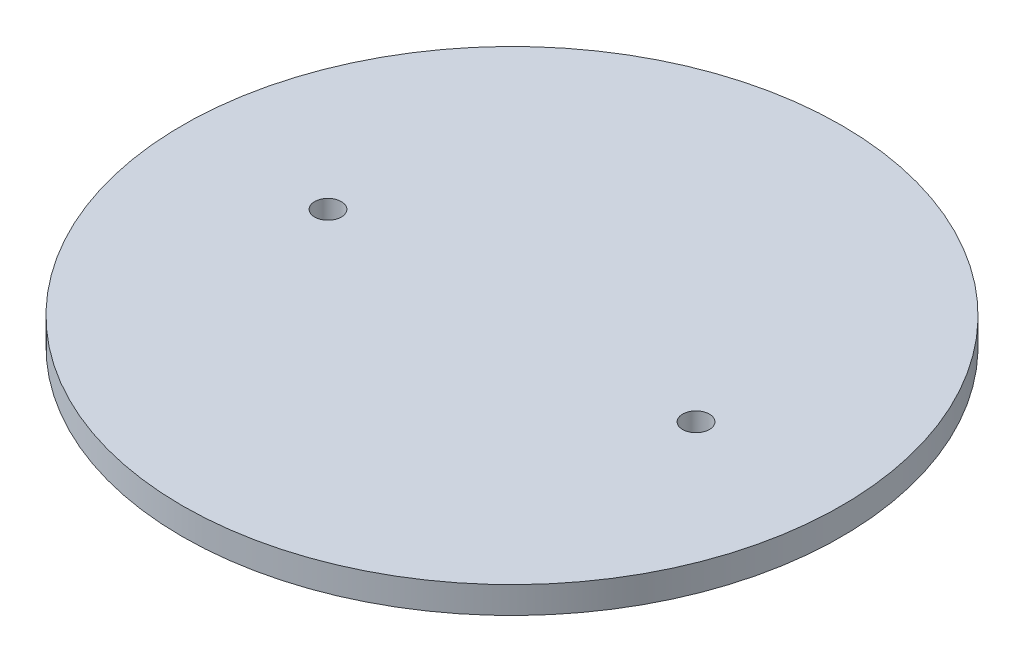
SolidWorks part; units mm, degrees
material "Balsa"
ref_plane "Front Plane" through (0, 0, 0) normal (0, 0, 1) x (1, 0, 0)
ref_plane "Top Plane" through (0, 0, 0) normal (0, 1, 0) x (1, 0, 0)
ref_plane "Right Plane" through (0, 0, 0) normal (1, 0, 0) x (0, 0, -1)
sketch "Sketch1" plane through (0, 0, 0) normal (0, 1, 0) x (1, 0, 0)
  line L0 (-49.25, 0) -> (49.25, 0) construction
  line L1 (0, 49.25) -> (0, -49.25) construction
  circle A0 centre (0, 0) radius 49.25
  circle A1 centre (-27.5, 0) radius 2
  circle A2 centre (27.5, 0) radius 2
  dimension "D1" = 55
extrude "Boss-Extrude1" add sketch "Sketch1" along normal blind 4
